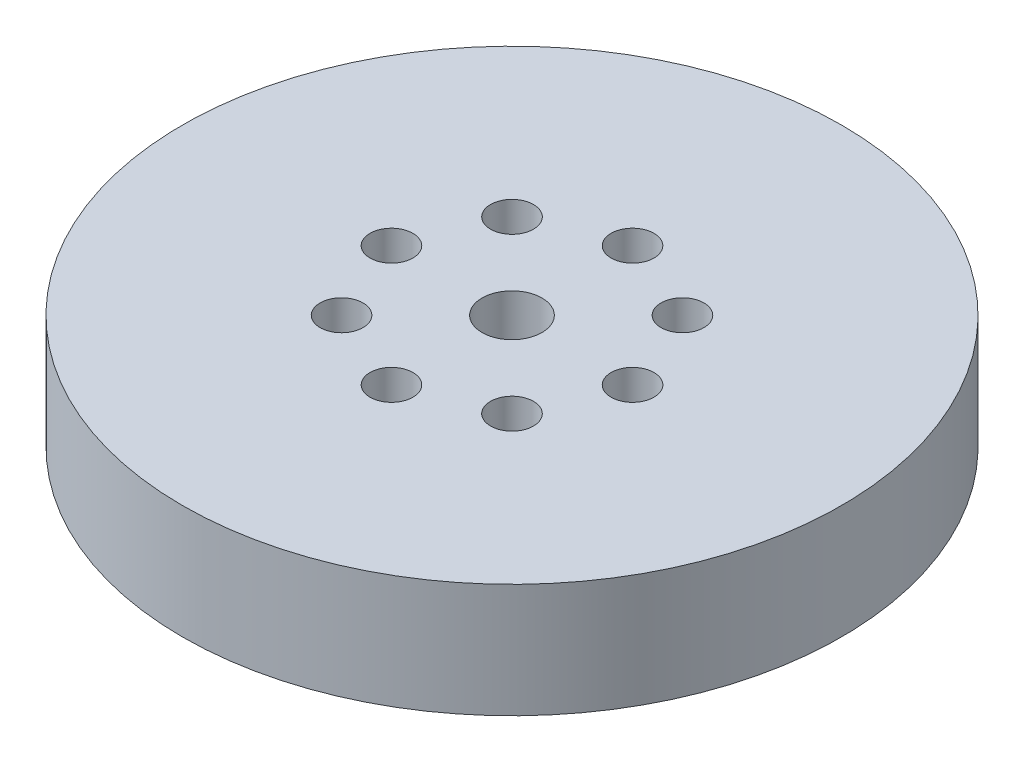
SolidWorks part; units mm, degrees
ref_plane "Front Plane" through (0, 0, 0) normal (0, 0, 1) x (1, 0, 0)
ref_plane "Top Plane" through (0, 0, 0) normal (0, 1, 0) x (1, 0, 0)
ref_plane "Right Plane" through (0, 0, 0) normal (1, 0, 0) x (0, 0, -1)
sketch "Sketch1" plane through (0, 0, 0) normal (0, 1, 0) x (1, 0, 0)
  circle A0 centre (0, 0) radius 55
  dimension "FLANGE_OD" = 110
extrude "Boss-Extrude1" add sketch "Sketch1" along normal blind 19
sketch "Sketch2" plane through (0, 0, 0) normal (0, 1, 0) x (1, 0, 0)
  circle A0 centre (0, 0) radius 5
  dimension "BORE_D" = 10
extrude "Cut-Extrude1" cut sketch "Sketch2" along normal through all
sketch "Sketch3" plane through (0, 19, 0) normal (0, 1, 0) x (1, 0, 0)
  circle A0 centre (0, 0) radius 20.1163 construction
  circle A1 centre (-20.1163, 0) radius 3.5782
  dimension "BOLT_D" = 7.1564
  dimension "BOLT_PCD" = 40.2326
extrude "Cut-Extrude2" cut sketch "Sketch3" against normal blind 18.2594
pattern_circular "CirPattern1" count 8 over 360 about axis through (0, 0, 0) along (0, 1, 0) of "Cut-Extrude2"
